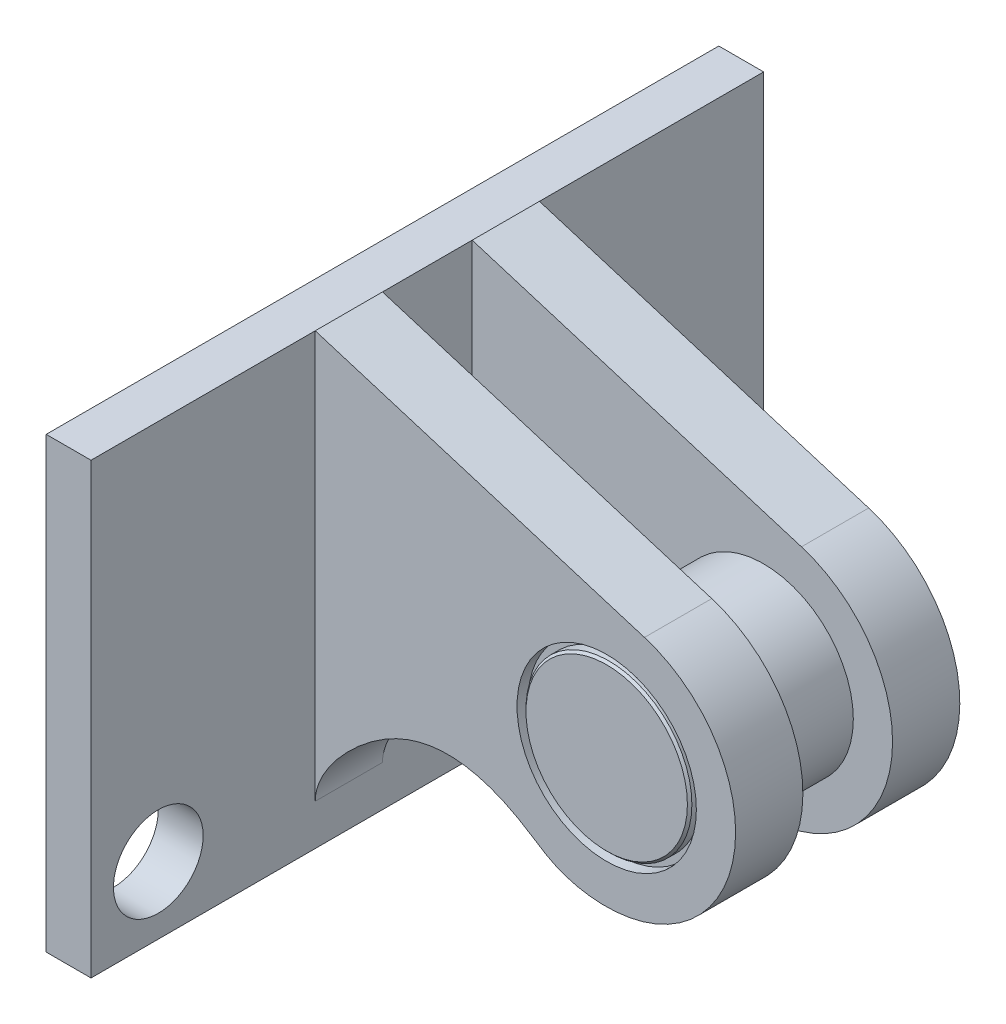
SolidWorks part; units mm, degrees
ref_plane "Alzado" through (0, 0, 0) normal (0, 0, 1) x (1, 0, 0)
ref_plane "Planta" through (0, 0, 0) normal (0, 1, 0) x (1, 0, 0)
ref_plane "Vista lateral" through (0, 0, 0) normal (1, 0, 0) x (0, 0, -1)
sketch "Croquis1" plane through (0, 0, 0) normal (0, 0, 1) x (1, 0, 0)
sketch_block_instance "chumacera-2"
sketch_block "chumacera" parameters "D1"=8, "D2"=15, "D3"=7
ref_plane "Plano1" through (4.6598, 0, 0) normal (1, 0, 0) x (0, 0, -1)
sketch "Croquis2" plane through (4.6598, 0, 0) normal (1, 0, 0) x (0, 0, -1)
  line L1 (-15, -22.0058) -> (15, -22.0058)
  line L2 (-15, -22.0058) -> (-15, -2.0058)
  line L3 (-15, -2.0058) -> (15, -2.0058)
  line L4 (15, -22.0058) -> (15, -2.0058)
  line L5 (-15, -22.0058) -> (15, -2.0058) construction
  line L6 (-15, -2.0058) -> (15, -22.0058) construction
  point P0 (0, -12.0058)
  point P2 (0, -12.0058)
  dimension "D1" = 30
  dimension "D2" = 20
extrude "Saliente-Extruir1" add sketch "Croquis2" along normal blind 2
ref_plane "Plano2" through (0, 0, 2) normal (0, 0, 1) x (1, 0, 0)
sketch "Croquis3" plane through (0, 0, 2) normal (0, 0, 1) x (1, 0, 0)
  line L0 (4.6598, -12.0058) -> (19.6598, -12.0058) construction
  line L1 (4.6598, -12.0058) -> (19.6598, -12.0058) construction
  line L2 (6.6598, -2.0058) -> (6.6598, -22.0058) construction
  line L3 (6.6598, -2.0058) -> (6.6598, -20.1789)
  line L4 (6.6598, -2.0058) -> (21.3453, -6.5084)
  line L5 (6.6598, -20.1789) -> (20.6748, -17.6655) construction
  circle A0 centre (19.6598, -12.0058) radius 4 construction
  circle A1 centre (19.6598, -12.0058) radius 4
  circle A2 centre (19.6598, -12.0058) radius 5.75 construction
  arc A3 (20.6748, -17.6655) -> (21.3453, -6.5084) centre (19.6598, -12.0058) ccw
  spline S0 degree 3 poles (20.6748, -17.6655) (19.5349, -17.8699) (17.7927, -17.715) (14.4778, -15.3673) (10.5194, -14.5252) (6.6598, -19.0081) (6.6598, -20.1789) knots 0 0 0 0 0.229346 0.306026 0.766799 1 1 1 1
  point P10 (21.0666, -16.8109)
  point P12 (22.3026, -17.5234)
  point P13 (10.6657, -17.2658)
  point P15 (10.2489, -16.2848)
  point P16 (0, 0)
  point P17 (15.5737, -16.0513)
  point P18 (16.8097, -16.9997)
  point P19 (9.2204, -16.5871)
  dimension "D1" = 5.75
extrude "Saliente-Extruir2" add sketch "Croquis3" along normal blind 3 contours L5 A3 L4 L3 A1 region at (13.6485, -10.3204, 2)
mirror "Simetría1" about plane through (0, 0, 0) normal (0, 0, 1) of "Saliente-Extruir2"
sketch "Croquis4" plane through (6.6598, 0, 0) normal (1, 0, 0) x (0, 0, -1)
  line L0 (-15, -22.0058) -> (15, -22.0058) construction
  line L1 (-15, -2.0058) -> (-15, -22.0058) construction
  circle A0 centre (-12, -19.0058) radius 2
  dimension "D1" = 3
  dimension "D3" = 4
  dimension "D2" = 3
extrude "Cortar-Extruir1" cut sketch "Croquis4" against normal up to next
sketch "Croquis5" plane through (0, 0, 5) normal (0, 0, 1) x (1, 0, 0)
  circle A0 centre (19.6598, -12.0058) radius 4 construction
  circle A1 centre (19.6598, -12.0058) radius 4
extrude "Saliente-Extruir3" add sketch "Croquis5" against normal up to surface (10 mm away) separate body up to face at (16.6841, -11.3414, -5)
sketch "Croquis6" plane through (0, 0, 5) normal (0, 0, 1) x (1, 0, 0)
  circle A0 centre (19.6598, -12.0058) radius 4 construction
  circle A1 centre (19.6598, -12.0058) radius 4
  circle A2 centre (19.6598, -12.0058) radius 3.7
  dimension "D1" = 0.3
extrude "Cortar-Extruir2" cut sketch "Croquis6" against normal blind 0.5
chamfer "Chaflán1" distance 0.1 angle 45 1 edges at (23.3598, -12.0058, 5)
mirror "Simetría3" about plane through (0, 0, 0) normal (0, 0, 1) of "Cortar-Extruir2"
chamfer "Chaflán2" distance 0.1 angle 45 1 edges at (23.3598, -12.0058, -5)
